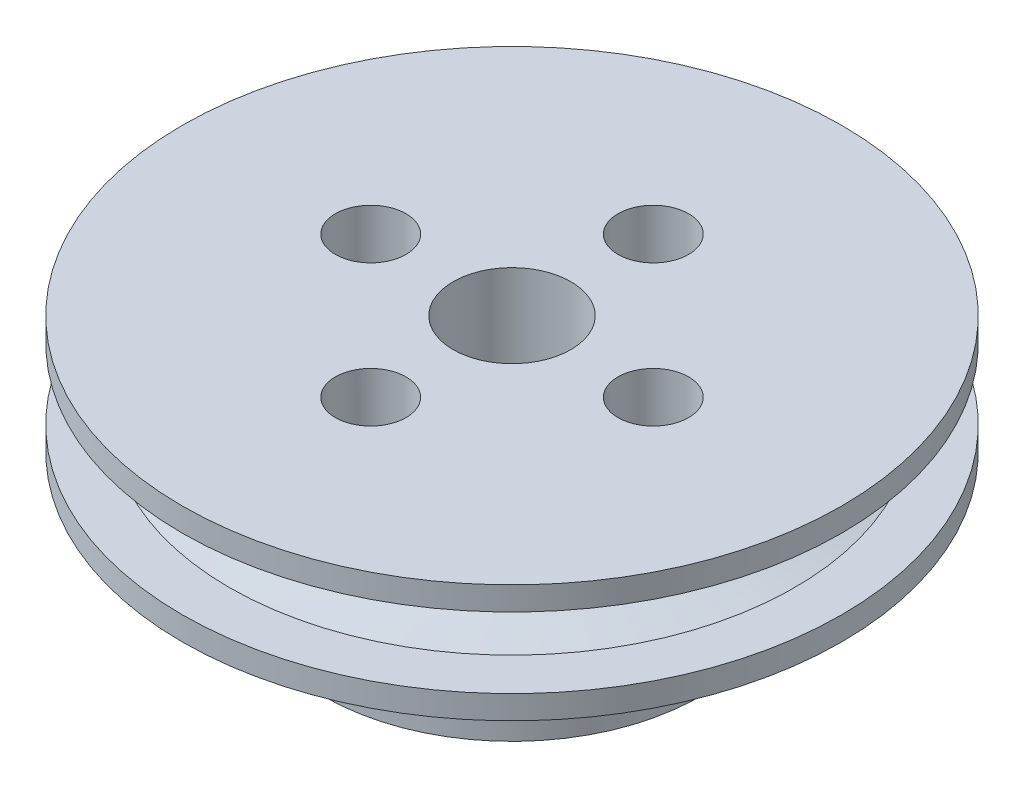
SolidWorks part; units mm, degrees
other "标注1"
sketch "草图9" plane through (-14, 10, 14) normal (-0.1667, 0.2364, 0.9573) x (0.9581, 0.2681, 0.1006)
other "标注2"
sketch "草图10"
material "ABS"
ref_plane "前视基准面" through (0, 0, 0) normal (0, 0, 1) x (1, 0, 0)
ref_plane "上视基准面" through (0, 0, 0) normal (0, 1, 0) x (1, 0, 0)
ref_plane "右视基准面" through (0, 0, 0) normal (1, 0, 0) x (0, 0, -1)
sketch "草图1" plane through (0, 0, 0) normal (0, 1, 0) x (1, 0, 0)
  circle A0 centre (0, 0) radius 8
  dimension "D1" = 16
extrude "凸台-拉伸1" add sketch "草图1" along normal blind 5
sketch "草图3" plane through (0, 0, 0) normal (0, 0, 1) x (1, 0, 0)
  line L0 (2.5, 5) -> (12, 5)
  line L1 (8, 5) -> (-8, 5) construction
  line L3 (12, 10) -> (2.5, 10)
  line L4 (0, 11) -> (0, 5) construction
  line L5 (12, 9) -> (12, 10)
  line L6 (12, 6) -> (12, 5)
  line L7 (2.5, 10) -> (2.5, 5)
  line L8 (12, 10) -> (14.0186, 10)
  line L9 (14.0186, 10) -> (14.0186, 9)
  line L10 (12, 9) -> (12, 6)
  line L11 (9, 7.5) -> (2.5, 7.5)
  spline S0 degree 4 poles (12.6644, 5.7868) (12.6335, 5.7968) (12.5806, 5.8139) (12.5498, 5.8242) (12.3125, 5.9004) (12.0321, 5.9899) (11.7628, 6.0752) (11.1308, 6.278) (10.8538, 6.3743) (10.4624, 6.5112) (10.3431, 6.5596) (10.1924, 6.6167) (10.1356, 6.6406) (10.0445, 6.6776) (9.9437, 6.7207) (9.8097, 6.7804) (9.6488, 6.8581) (9.471, 6.9535) (9.3035, 7.0608) (9.1707, 7.1685) (9.0813, 7.2708) (9.0343, 7.3491) (9.0097, 7.4144) (8.9991, 7.473) (8.9993, 7.5298) (9.0105, 7.5885) (9.0358, 7.654) (9.0837, 7.7325) (9.1547, 7.8126) (9.2439, 7.8908) (9.3633, 7.9775) (9.4804, 8.0499) (9.5998, 8.1154) (9.725, 8.1789) (9.8435, 8.2344) (9.962, 8.2881) (10.0939, 8.3423) (10.1801, 8.3786) (10.3472, 8.442) (10.4683, 8.4909) (10.8575, 8.627) (11.1337, 8.7229) (11.7644, 8.9253) (12.0322, 9.0101) (12.3131, 9.0998) (12.5493, 9.1756) (12.5808, 9.1861) (12.6336, 9.2032) (12.6643, 9.2132) knots 0 0 0 0 0 0.010416 0.020831 0.041663 0.083326 0.1552 0.227075 0.263013 0.29895 0.307934 0.316919 0.325903 0.334887 0.352856 0.370825 0.396081 0.421338 0.449866 0.466732 0.47811 0.486548 0.493647 0.500181 0.506692 0.513762 0.522298 0.533856 0.550816 0.565113 0.579411 0.604782 0.617467 0.630153 0.648061 0.665968 0.683876 0.692829 0.701783 0.737598 0.773414 0.845044 0.916674 0.958337 0.979169 0.989584 1 1 1 1 1 construction
  spline S1 degree 4 poles (12, 6) (11.8816, 6.0377) (11.6438, 6.1134) (11.1308, 6.278) (10.8538, 6.3743) (10.4624, 6.5112) (10.3431, 6.5596) (10.1924, 6.6167) (10.1356, 6.6406) (10.0445, 6.6776) (9.9437, 6.7207) (9.8097, 6.7804) (9.6488, 6.8581) (9.471, 6.9535) (9.3035, 7.0608) (9.1707, 7.1685) (9.0813, 7.2708) (9.0343, 7.3491) (9.0097, 7.4144) (8.9991, 7.473) (8.9993, 7.5298) (9.0105, 7.5885) (9.0358, 7.654) (9.0837, 7.7325) (9.1547, 7.8126) (9.2439, 7.8908) (9.3633, 7.9775) (9.4804, 8.0499) (9.5998, 8.1154) (9.725, 8.1789) (9.8435, 8.2344) (9.962, 8.2881) (10.0939, 8.3423) (10.1801, 8.3786) (10.3472, 8.442) (10.4683, 8.4909) (10.8575, 8.627) (11.1337, 8.7229) (11.6454, 8.8871) (11.882, 8.9624) (12, 9) knots 0.083326 0.083326 0.083326 0.083326 0.083326 0.1552 0.227075 0.263013 0.29895 0.307934 0.316919 0.325903 0.334887 0.352856 0.370825 0.396081 0.421338 0.449866 0.466732 0.47811 0.486548 0.493647 0.500181 0.506692 0.513762 0.522298 0.533856 0.550816 0.565113 0.579411 0.604782 0.617467 0.630153 0.648061 0.665968 0.683876 0.692829 0.701783 0.737598 0.773414 0.845044 0.916674 0.916674 0.916674 0.916674 0.916674
  point P4 (12, 9)
  point P7 (12, 6)
  dimension "D1" = 5
  dimension "D2" = 9.5
  dimension "D3" = 1
  dimension "D4" = 1
  dimension "D5" = 2.5
  dimension "D6" = 6.5
revolve "旋转3" add sketch "草图3" angle 360 about L4
sketch "草图4" plane through (0, 10, 0) normal (0, 1, 0) x (1, 0, 0)
  circle A0 centre (0, 0) radius 6 construction
  circle A1 centre (0, 6) radius 1.5
  circle A2 centre (6, 0) radius 1.5
  circle A3 centre (0, -6) radius 1.5
  circle A4 centre (-6, 0) radius 1.5
  point P14 (0, 0)
  dimension "D1" = 4
  dimension "D2" = 3
  dimension "D3" = 12
extrude "切除-拉伸1" cut sketch "草图4" against normal blind 5
sketch "草图5" plane through (0, 5, 0) normal (0, 1, 0) x (1, 0, 0)
  circle A0 centre (0, 6) radius 1.05
  circle A1 centre (-6, 0) radius 1.05
  circle A2 centre (6, 0) radius 1.05
  circle A3 centre (0, -6) radius 1.05
  dimension "D1" = 2.1
  dimension "D2" = 2.1
  dimension "D3" = 2.1
  dimension "D4" = 2.1
extrude "切除-拉伸2" cut sketch "草图5" against normal up to surface (5 mm away) up to face at (0, 0, 8)
sketch "草图6" plane through (0, 0, 0) normal (1, 0, 0) x (0, 0, -1)
  line L0 (-12, 9) -> (12, 6) construction
  line L1 (12, 6) -> (12, 9) construction
  line L2 (12, 9) -> (-12, 6) construction
  line L3 (-12, 6) -> (-12, 9) construction
  line L4 (0, 7.5) -> (-12, 7.5) construction
  circle A0 centre (-6, 7.5) radius 0.75
  spline S0 degree 4 poles (-12, 9) (-11.882, 8.9624) (-11.6454, 8.8871) (-11.1337, 8.7229) (-10.8575, 8.627) (-10.4683, 8.4909) (-10.3472, 8.442) (-10.1801, 8.3786) (-10.0939, 8.3423) (-9.962, 8.2881) (-9.8435, 8.2344) (-9.725, 8.1789) (-9.5998, 8.1154) (-9.4804, 8.0499) (-9.3633, 7.9775) (-9.2439, 7.8908) (-9.1547, 7.8126) (-9.0837, 7.7325) (-9.0358, 7.654) (-9.0105, 7.5885) (-8.9993, 7.5298) (-8.9991, 7.473) (-9.0097, 7.4144) (-9.0343, 7.3491) (-9.0813, 7.2708) (-9.1707, 7.1685) (-9.3035, 7.0608) (-9.471, 6.9535) (-9.6488, 6.8581) (-9.8097, 6.7804) (-9.9437, 6.7207) (-10.0445, 6.6776) (-10.1356, 6.6406) (-10.1924, 6.6167) (-10.3431, 6.5596) (-10.4624, 6.5112) (-10.8538, 6.3743) (-11.1308, 6.278) (-11.6438, 6.1134) (-11.8816, 6.0377) (-12, 6) knots 0.083326 0.083326 0.083326 0.083326 0.083326 0.154956 0.226586 0.262402 0.298217 0.307171 0.316124 0.334032 0.351939 0.369847 0.382533 0.395218 0.420589 0.434887 0.449184 0.466144 0.477702 0.486238 0.493308 0.499819 0.506353 0.513452 0.52189 0.533268 0.550134 0.578662 0.603919 0.629175 0.647144 0.665113 0.674097 0.683081 0.692066 0.70105 0.736987 0.772925 0.8448 0.916674 0.916674 0.916674 0.916674 0.916674 construction
  point P12 (-9, 7.5)
  dimension "D1" = 3
  dimension "D2" = 1.5
extrude "切除-拉伸3" cut sketch "草图6" against normal through all both and the other way through all
ref_axis "基准轴1" through (1.2472, 7.5, 6) along (1, 0, 0)
ref_plane "基准面1" through (0, 7.5, 0) normal (0, 1, 0) x (1, 0, 0)
ref_plane "基准面2" through (0, 0, 6) normal (0, 0, 1) x (1, 0, 0)
ref_plane "基准面3" through (0, 0, 9) normal (0, 0, 1) x (1, 0, 0)
ref_axis "切线" through (-13.2, 7.5, 9) along (1, 0, 0)
fillet "圆角1" radius 2 1 edges at (0, 5, 8) type face fillet first side face at (0, 5, 8) second side face at (0, 5, 8)
sketch "草图7" plane through (0, 5, 0) normal (0, 1, 0) x (1, 0, 0)
  circle A0 centre (0, 0) radius 2.5
  dimension "D1" = 5
extrude "切除-拉伸4" cut sketch "草图7" against normal through all
sketch "草图8" plane through (0, 0, 0) normal (0, 0, 1) x (1, 0, 0)
  line L0 (12, 10) -> (12, 9)
  line L1 (12, 9) -> (14, 9)
  line L2 (14, 9) -> (14, 10)
  line L3 (14, 10) -> (12, 10)
  line L4 (12, 6) -> (12, 5)
  line L5 (12, 5) -> (14, 5)
  line L6 (14, 5) -> (14, 6)
  line L7 (14, 6) -> (12, 6)
  line L8 (-12, 6) -> (12, 6) construction
  line L9 (-12, 9) -> (12, 9) construction
  line L10 (0, 9) -> (0, 6) construction
  dimension "D1" = 2
  dimension "D2" = 2
revolve "旋转4" add sketch "草图8" angle 360 about L10
